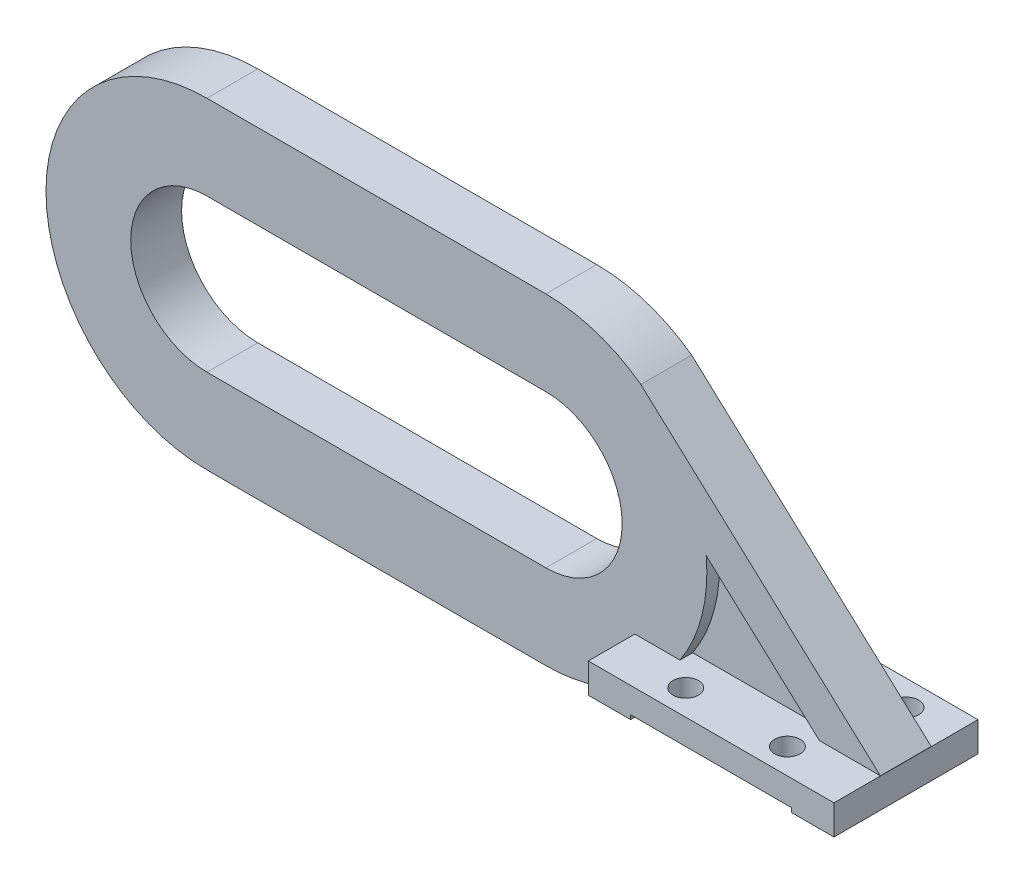
SolidWorks part; units mm, degrees
ref_plane "Front Plane" through (0, 0, 0) normal (0, 0, 1) x (1, 0, 0)
ref_plane "Top Plane" through (0, 0, 0) normal (0, 1, 0) x (1, 0, 0)
ref_plane "Right Plane" through (0, 0, 0) normal (1, 0, 0) x (0, 0, -1)
sketch "Sketch1" plane through (0, 0, 0) normal (0, 1, 0) x (1, 0, 0)
  line L0 (-6, -5.5) -> (6, -5.5)
  line L1 (-13.5, 7.5) -> (13.5, 7.5)
  line L2 (-13.5, 7.5) -> (-13.5, -7.5)
  line L3 (-13.5, -7.5) -> (13.5, -7.5)
  line L4 (13.5, 7.5) -> (13.5, -7.5)
  line L5 (-13.5, 7.5) -> (13.5, -7.5) construction
  line L6 (-13.5, -7.5) -> (13.5, 7.5) construction
  line L7 (-9, 5.5) -> (9, 5.5) construction
  line L8 (-9, 5.5) -> (-9, -5.5) construction
  line L9 (-9, -5.5) -> (9, -5.5) construction
  line L10 (9, 5.5) -> (9, -5.5) construction
  line L11 (-9, 5.5) -> (9, -5.5) construction
  line L12 (-9, -5.5) -> (9, 5.5) construction
  line L13 (-14.5, 8.5) -> (14.5, 8.5)
  line L14 (14.5, 8.5) -> (14.5, -8.5)
  line L15 (-14.5, -8.5) -> (14.5, -8.5)
  line L16 (-14.5, 8.5) -> (-14.5, -8.5)
  circle A0 centre (-9, 5.5) radius 1.5
  circle A1 centre (9, 5.5) radius 1.5
  circle A2 centre (-6, -5.5) radius 1.5
  circle A3 centre (6, -5.5) radius 1.5
  point P0 (0, 0)
  point P6 (0, 0)
  point P16 (0, -5.5)
  dimension "D6" = 3
  dimension "D1" = 27
  dimension "D2" = 15
  dimension "D3" = 18
  dimension "D4" = 11
  dimension "D5" = 12
  dimension "D7" = 1
extrude "Boss-Extrude1" add sketch "Sketch1" along normal blind 3 contours L4 L1 L2 L3 A3 A2 A1 A0 | L13 L16 L15 L14 L1 L4 L3 L2 region at (0, 0, 0) region at (0, 0, -8.1638)
extrude "Boss-Extrude2" add sketch "Sketch1<3>" against normal blind 0.5 contours L13 L16 L15 L14 L1 L4 L3 L2 region at (0, 0, -8.1638)
sketch "Sketch1<3>" plane through (0, 0, 0) normal (0, 1, 0) x (1, 0, 0) same geometry as "Sketch1"
sketch "Sketch3" plane through (0, 0, 8.5) normal (0, 0, 1) x (1, 0, 0)
  line L0 (-14.5, -0.5) -> (14.5, -0.5) construction
  line L1 (-9.5, 0) -> (9.5, 0)
  line L2 (-9.5, 0) -> (-9.5, -1)
  line L3 (-9.5, -1) -> (9.5, -1)
  line L4 (9.5, 0) -> (9.5, -1)
  line L5 (-9.5, 0) -> (9.5, -1) construction
  line L6 (-9.5, -1) -> (9.5, 0) construction
  line L7 (-13.5, 0) -> (13.5, 0) construction
  line L8 (-13.5, -0.5) -> (-13.5, 0) construction
  point P0 (0, -0.5)
  dimension "D1" = 4
extrude "Cut-Extrude1" cut sketch "Sketch3" against normal blind 6
sketch "Sketch4" plane through (0, 0, 0) normal (0, 0, 1) x (1, 0, 0)
  line L0 (-25, 13.517) -> (-65, 13.517) construction
  line L1 (-25, 4.517) -> (-65, 4.517)
  line L2 (-25, 22.517) -> (-65, 22.517)
  line L3 (-25, -5.483) -> (-65, -5.483)
  line L4 (-25, 32.517) -> (-65, 32.517)
  line L5 (-14.5, 3) -> (14.4764, 3)
  line L6 (14.4764, 3) -> (-13.7993, 28.8645)
  line L7 (-14.5, 3) -> (-14.5, -2.318)
  line L8 (-14.5, 3) -> (-14.5, -0.5) construction
  line L9 (7.5, 3) -> (4.5, 3) construction
  line L10 (7.2827, 3) -> (-10.6386, 19.3931)
  line L11 (-10.6386, 19.3931) -> (-10.6386, 3)
  arc A0 (-25, 4.517) -> (-25, 22.517) centre (-25, 13.517) ccw
  arc A1 (-65, 22.517) -> (-65, 4.517) centre (-65, 13.517) ccw
  arc A2 (-65, 32.517) -> (-65, -5.483) centre (-65, 13.517) ccw
  arc A3 (-25, -5.483) -> (-25, 32.517) centre (-25, 13.517) ccw
  point P2 (-45, 13.517)
  dimension "D3" = 9
  dimension "D1" = 25
  dimension "D2" = 40
  dimension "D4" = 10
extrude "Boss-Extrude3" add sketch "Sketch4" along normal mid plane 6 contours L5 A3 L10 L11 | L10 A3 L6 L4 A2 L3 L7 L5 L11 A1 L2 A0 L1 | A3 L10 L5 L6 region at (-45, -4.616, 0) region at (-8.7258, 11.0768, 0) region at (1.8858, 11.5556, 0)
extrude "Boss-Extrude4" add sketch "Sketch4<3>" along normal mid plane 3 contours A3 L5 L10 region at (-2.204, 6.8813, 0)
sketch "Sketch4<3>" plane through (0, 0, 0) normal (0, 0, 1) x (1, 0, 0) same geometry as "Sketch4"
